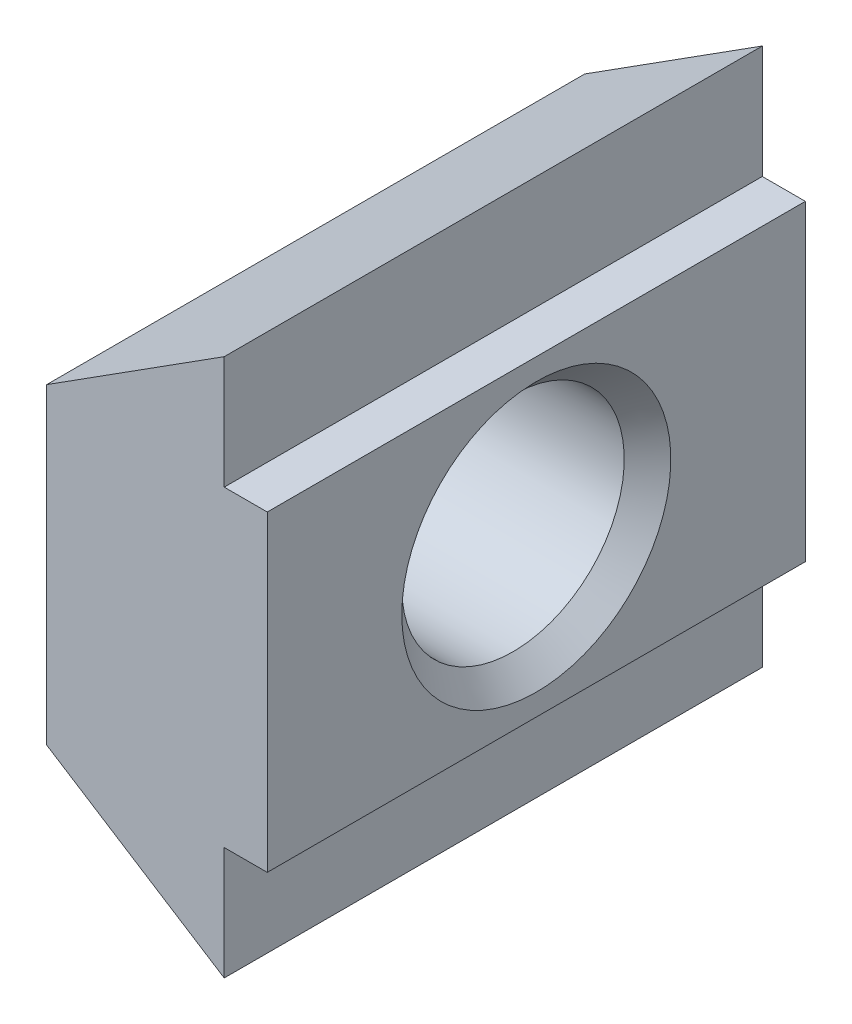
SolidWorks part; units mm, degrees
ref_plane "前基準面" through (0, 0, 0) normal (0, 0, 1) x (1, 0, 0)
ref_plane "上基準面" through (0, 0, 0) normal (0, 1, 0) x (1, 0, 0)
ref_plane "右基準面" through (0, 0, 0) normal (1, 0, 0) x (0, 0, -1)
ref_plane "平面1" through (0, 0, 0) normal (0, 0, 1) x (1, 0, 0)
sketch "草圖1" plane through (0, 0, 0) normal (0, 0, 1) x (1, 0, 0)
  line L0 (-4.1, 2.9) -> (-4.1, -2.9)
  line L1 (-4.1, -2.9) -> (-0.8, -5)
  line L2 (-0.8, -5) -> (-0.8, -2.9)
  line L3 (-0.8, -2.9) -> (0, -2.9)
  line L4 (0, -2.9) -> (0, 2.9)
  line L5 (0, 2.9) -> (-0.8, 2.9)
  line L6 (-0.8, 2.9) -> (-0.8, 5)
  line L7 (-0.8, 5) -> (-4.1, 2.9)
extrude "填料-伸長1" add sketch "草圖1" against normal blind 5 and the other way blind 5
ref_plane "平面2" through (0, 0, 0) normal (0, 0, 1) x (1, 0, 0)
sketch "草圖2" plane through (0, 0, 0) normal (0, 0, 1) x (1, 0, 0)
  line L0 (-4.1, 0) -> (-4.1, 2.5)
  line L1 (-4.1, 2.5) -> (-3.667, 2.067)
  line L2 (-3.667, 2.067) -> (-0.433, 2.067)
  line L3 (-0.433, 2.067) -> (0, 2.5)
  line L4 (0, 2.5) -> (0, 0)
  line L5 (0, 0) -> (-4.1, 0)
  line L6 (0, 0) -> (-4.1, 0) construction
revolve "除料-旋轉1" cut sketch "草圖2" angle 360 about L6 reverse direction yes
cosmetic thread "裝飾螺紋線1" parameters "D1"=4.1, "D2"=5
